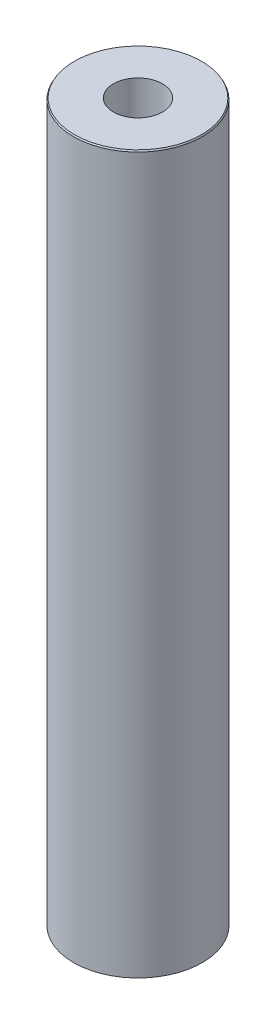
SolidWorks part; units mm, degrees
ref_plane "Front Plane" through (0, 0, 0) normal (0, 0, 1) x (1, 0, 0)
ref_plane "Top Plane" through (0, 0, 0) normal (0, 1, 0) x (1, 0, 0)
ref_plane "Right Plane" through (0, 0, 0) normal (1, 0, 0) x (0, 0, -1)
sketch "Sketch1" plane through (0, 0, 0) normal (0, 1, 0) x (1, 0, 0)
  circle A0 centre (0, 0) radius 40
  dimension "SHAFT_OD" = 80
extrude "Boss-Extrude1" add sketch "Sketch1" along normal blind 445.6235
sketch "Sketch2" plane through (0, 0, 0) normal (0, 1, 0) x (1, 0, 0)
  circle A0 centre (0, 0) radius 15.2316
  dimension "BORE_D" = 30.4632
extrude "Cut-Extrude1" cut sketch "Sketch2" along normal through all
chamfer "Chamfer1" distance 0.8709 angle 30 2 edges at (0, 445.6235, 40) (0, 0, 40) first distance on face at (0, 445.6235, 40) first distance on face at (0, 0, 15.2316)
